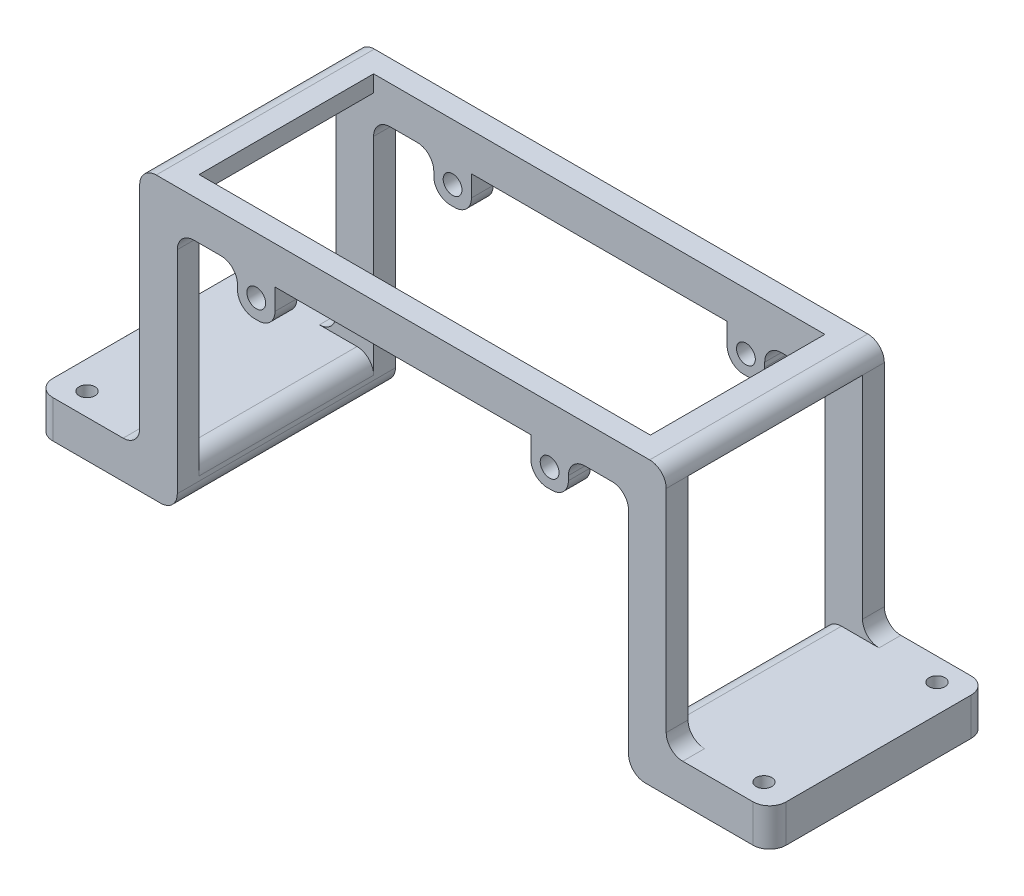
SolidWorks part; units mm, degrees
material "eSUN Tough Resin"
ref_plane "Front Plane" through (0, 0, 0) normal (0, 0, 1) x (1, 0, 0)
ref_plane "Top Plane" through (0, 0, 0) normal (0, 1, 0) x (1, 0, 0)
ref_plane "Right Plane" through (0, 0, 0) normal (1, 0, 0) x (0, 0, -1)
ref_plane "Plane1" through (0, 0, -23) normal (0, 0, 1) x (1, 0, 0)
ref_plane "Mirror Plane" through (0, 0, -11.5) normal (0, 0, 1) x (1, 0, 0)
sketch "Sketch1" plane through (0, 0, 0) normal (0, 0, 1) x (1, 0, 0)
  line L0 (0, -5.5178) -> (0, 1.5946) construction
  line L2 (-30, -30) -> (-30, 2.5)
  line L3 (-30, 2.5) -> (-22, 2.5)
  line L11 (0, 7.5) -> (-35, 7.5)
  line L12 (-35, 7.5) -> (-35, -25)
  line L13 (-35, -25) -> (-48.75, -25)
  line L17 (-48.75, -30) -> (-30, -30)
  line L18 (0, 7.5) -> (0, 2.5)
  line L19 (-17, 2.5) -> (0, 2.5)
  line L20 (-48.75, -30) -> (-48.75, -25)
  line L21 (-22, -2.5) -> (-17, -2.5)
  line L22 (-22, -2.5) -> (-22, 2.5)
  line L24 (-17, -2.5) -> (-17, 2.5)
  line L25 (-22, -2.5) -> (-17, 2.5) construction
  line L26 (-22, 2.5) -> (-17, -2.5) construction
  circle A0 centre (-19.5, 0) radius 1.25
  point P13 (-45, -25)
  dimension "D2" = 2.5
  dimension "D1" = 19.5
  dimension "D3" = 5
  dimension "D4" = 5
  dimension "D5" = 3.75
  dimension "D6" = 45
  dimension "D7" = 25
  dimension "D8" = 10
extrude "Boss-Extrude1" add sketch "Sketch1" against normal offset from surface 3 and the other way blind 3 up to plane "Plane1" offset beyond the face yes
sketch "Sketch2" plane through (0, -25, 0) normal (0, 1, 0) x (1, 0, 0)
  line L1 (-48.75, 11.5) -> (-35, 11.5) construction
  line L2 (-48.75, -3) -> (-48.75, 26) construction
  line L3 (-35, -3) -> (-35, 26) construction
  circle A0 centre (-45, 23) radius 1.05
  circle A1 centre (-45, 0) radius 1.05
  dimension "D1" = 2.1
  dimension "D2" = 23
extrude "Cut-Extrude1" cut sketch "Sketch2" against normal through all
mirror "Mirror1" about plane through (0, 0, 0) normal (1, 0, 0) of "Cut-Extrude1", "Boss-Extrude1"
fillet "Fillet1" radius 2.2 18 edges at (-30, -30, -11.5) (-30, 2.5, -11.5) (22, 2.5, -11.5) (22, -2.5, -11.5) (30, 2.5, -11.5) (-22, 2.5, -11.5) (-22, -2.5, -11.5) (-17, -2.5, -11.5) (17, -2.5, -11.5) (30, -30, -11.5) (35, -25, -11.5) (35, 7.5, -11.5) (-35, 7.5, -11.5) (-35, -25, -11.5) (48.75, -27.5, 3) (48.75, -27.5, -26) (-48.75, -27.5, 3) (-48.75, -27.5, -26)
sketch "Sketch3" plane through (0, 0, 0) normal (0, 1, 0) x (1, 0, 0)
  line L0 (-32.8, 26) -> (32.8, 26) construction
  line L1 (-30, 23.1) -> (30, 23.1)
  line L2 (-30, 23.1) -> (-30, -0.1)
  line L3 (-30, -0.1) -> (30, -0.1)
  line L4 (30, 23.1) -> (30, -0.1)
  line L5 (-30, 23.1) -> (30, -0.1) construction
  line L6 (-30, -0.1) -> (30, 23.1) construction
  line L7 (32.8, -3) -> (-32.8, -3) construction
  line L8 (30, 26) -> (30, -3) construction
  line L9 (-30, -3) -> (-30, 26) construction
  point P0 (0, 11.5)
  dimension "D1" = 2.9
  dimension "D2" = 2.9
extrude "Cut-Extrude2" cut sketch "Sketch3" along normal through all both and the other way through all
sketch "Sketch4" plane through (0, 0, 0) normal (1, 0, 0) x (0, 0, -1)
  line L1 (-0.1, -25) -> (23.1, -25)
  line L2 (-0.1, -25) -> (-0.1, 5.3)
  line L3 (-0.1, 5.3) -> (23.1, 5.3)
  line L4 (23.1, -25) -> (23.1, 5.3)
  line L5 (-0.1, -25) -> (23.1, 5.3) construction
  line L6 (-0.1, 5.3) -> (23.1, -25) construction
  line L7 (26, 5.3) -> (-3, 5.3) construction
  line L8 (23.1, 7.5) -> (23.1, 0.3) construction
  line L9 (-0.1, 7.5) -> (-0.1, 0.3) construction
  line L10 (26, -25) -> (-3, -25) construction
  point P0 (11.5, -9.85)
extrude "Cut-Extrude3" cut sketch "Sketch4" against normal through all both and the other way through all
fillet "Fillet2" radius 2.2 2 edges at (30, -25, -11.5) (-30, -25, -11.5)
equation "\"D4@Sketch1\"=\"D3@Sketch1\""
equation "\"D2@Sketch3\"=\"D1@Sketch3\""
